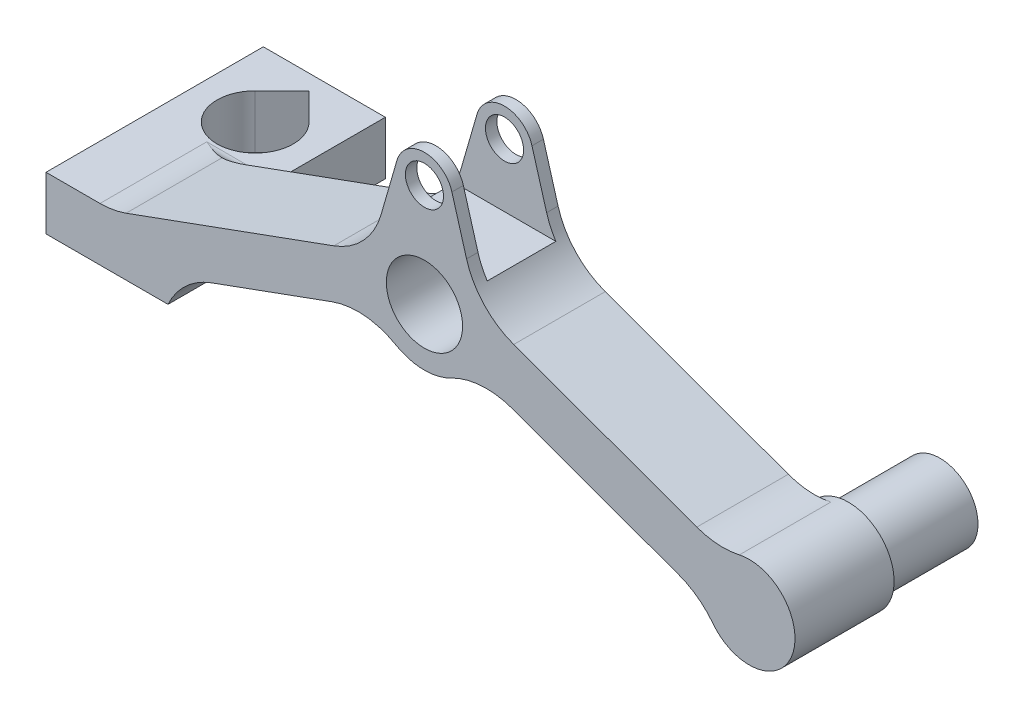
SolidWorks part; units mm, degrees
ref_plane "Alzado" through (0, 0, 0) normal (0, 0, 1) x (1, 0, 0)
ref_plane "Planta" through (0, 0, 0) normal (0, 1, 0) x (1, 0, 0)
ref_plane "Vista lateral" through (0, 0, 0) normal (1, 0, 0) x (0, 0, -1)
sketch "Croquis1" plane through (0, 0, 0) normal (0, 0, 1) x (1, 0, 0)
  line L0 (0, 0) -> (0, 13.5) construction
  line L1 (-3.6024, 14.5417) -> (-7.2048, 2.0833)
  line L2 (3.6024, 14.5417) -> (7.2048, 2.0833)
  circle A0 centre (0, 0) radius 5
  arc A1 (-7.2048, 2.0833) -> (7.2048, 2.0833) centre (0, 0) ccw
  circle A2 centre (0, 13.5) radius 2.5
  arc A3 (3.6024, 14.5417) -> (-3.6024, 14.5417) centre (0, 13.5) ccw
  dimension "D1" = 10
  dimension "D2" = 15
  dimension "D4" = 5
  dimension "D5" = 7.5
  dimension "D3" = 13.5
extrude "Saliente-Extruir1" add sketch "Croquis1" along normal mid plane 12
sketch "Croquis3" plane through (0, 0, 0) normal (1, 0, 0) x (0, 0, -1)
  line L0 (-4.5, 21.4548) -> (-4.5, 5.25)
  line L1 (-4.5, 5.25) -> (4.5, 5.25)
  line L2 (4.5, 5.25) -> (4.5, 21.4548)
  line L3 (4.5, 21.4548) -> (-4.5, 21.4548)
  line L4 (0, 0) -> (0, 21.4548) construction
  line L5 (6, 17.25) -> (-6, 17.25) construction
  point P7 (0, 21.4548)
  dimension "D1" = 9
  dimension "D2" = 12
extrude "Cortar-Extruir1" cut sketch "Croquis3" against normal through all both and the other way through all
sketch3d "Croquis3D1"
  line L0 (-5, 0, 0) -> (-41.6243, -13.3302, 0) construction
  line L1 (-41.6243, -13.3302, 0) -> (-41.6243, -13.3302, 8.998) construction
  line L2 (-41.6243, -13.3302, 8.998) -> (-5, 0, 0) construction
  line L3 (-5, 0, 0) -> (-41.6243, 0, 0) construction
  line L4 (-41.6243, 0, 0) -> (-41.6243, -13.3302, 0) construction
  line L5 (0, 0, 0) -> (-5, 0, 0) construction
  line L6 (-41.6243, -13.3302, 8.998) -> (-41.6243, -7.3302, 8.998) construction
  line L7 (0, 0, 0) -> (5, 0, 0) construction
  line L8 (5, 0, 0) -> (42.5877, -13.6808, 0) construction
  line L9 (5, 0, 0) -> (42.5877, 0, 0) construction
  line L10 (42.5877, 0, 0) -> (42.5877, -13.6808, 0) construction
  dimension "D1" = 40
  dimension "D2" = 13
  dimension "D3" = 20
  dimension "D4" = 5
  dimension "D5" = 6
  dimension "D6" = 5
  dimension "D7" = 20
  dimension "D8" = 40
ref_plane "Plano1" through (-41.6243, -13.3302, 0) normal (-0.9397, -0.342, 0) x (0, 0, 1)
sketch "Croquis4" plane through (-41.6243, -13.3302, 0) normal (-0.9397, -0.342, 0) x (0, 0, 1)
  line L1 (-6, 3) -> (6, 3)
  line L2 (-6, 3) -> (-6, -3)
  line L3 (-6, -3) -> (6, -3)
  line L4 (6, 3) -> (6, -3)
  line L5 (-6, 3) -> (6, -3) construction
  line L6 (-6, -3) -> (6, 3) construction
  point P0 (0, 0)
  dimension "D2" = 6
  dimension "D3" = 12
extrude "Saliente-Extruir2" add sketch "Croquis4" against normal blind 38
ref_plane "Plano2" through (-41.6243, -7.3302, 8.998) normal (0, 1, 0) x (1, 0, 0)
ref_plane "Plano3" through (42.5877, -13.6808, 0) normal (0.9397, -0.342, 0) x (0, 0, -1)
sketch "Croquis8" plane through (42.5877, -13.6808, 0) normal (0.9397, -0.342, 0) x (0, 0, -1)
  line L1 (-6, 3.5) -> (6, 3.5)
  line L2 (-6, 3.5) -> (-6, -3.5)
  line L3 (-6, -3.5) -> (6, -3.5)
  line L4 (6, 3.5) -> (6, -3.5)
  line L5 (-6, 3.5) -> (6, -3.5) construction
  line L6 (-6, -3.5) -> (6, 3.5) construction
  point P1 (0, 0)
  dimension "D1" = 12
  dimension "D2" = 7
extrude "Saliente-Extruir5" add sketch "Croquis8" against normal blind 39.5
sketch "Croquis9" plane through (0, 0, 0) normal (0, 0, 1) x (1, 0, 0)
  circle A0 centre (42.5877, -13.6808) radius 5
  dimension "D1" = 10
extrude "Saliente-Extruir6" add sketch "Croquis9" against normal blind 19
sketch "Croquis11" plane through (0, 0, 0) normal (0, 0, 1) x (1, 0, 0)
  line L1 (5, 0) -> (42.5877, -13.6808) construction
  line L2 (42.5877, 0) -> (42.5877, -13.6808) construction
  circle A0 centre (42.5877, -13.6808) radius 6
  dimension "D1" = 12
extrude "Saliente-Extruir7" add sketch "Croquis11" along normal mid plane 12
sketch "Croquis22" plane through (0, 0, 6) normal (0, 0, -1) x (-1, 0, 0)
  line L1 (33.6243, -16.8302) -> (49.6243, -16.8302)
  line L2 (33.6243, -16.8302) -> (33.6243, -9.8302)
  line L3 (33.6243, -9.8302) -> (49.6243, -9.8302)
  line L4 (49.6243, -16.8302) -> (49.6243, -9.8302)
  line L5 (33.6243, -16.8302) -> (49.6243, -9.8302) construction
  line L6 (33.6243, -9.8302) -> (49.6243, -16.8302) construction
  point P0 (41.6243, -13.3302)
  dimension "D1" = 7
  dimension "D2" = 16
extrude "Saliente-Extruir12" add sketch "Croquis22" along normal blind 28.5
sketch "Croquis24" plane through (0, -16.8302, 0) normal (0, -1, 0) x (1, 0, 0)
  line L0 (-41.6243, -31.5711) -> (-41.6243, -24.5) construction
  line L1 (-41.6243, -24.5) -> (-45.1599, -28.0355)
  line L2 (-41.6243, -24.5) -> (-38.0888, -28.0355)
  line L3 (-41.6243, -31.5711) -> (-41.6243, -22.5) construction
  line L4 (-33.6243, -22.5) -> (-49.6243, -22.5) construction
  line L5 (-41.6243, -22.5) -> (-43.4941, -22.5) construction
  line L6 (-33.6243, -22.5) -> (-49.6243, -22.5) construction
  line L7 (-41.6243, -20.5) -> (-38.0888, -16.9645)
  line L8 (-41.6243, -20.5) -> (-45.1599, -16.9645)
  arc A0 (-45.1599, -28.0355) -> (-38.0888, -28.0355) centre (-41.6243, -31.5711) ccw
  arc A1 (-45.1599, -16.9645) -> (-38.0888, -16.9645) centre (-41.6243, -13.4289) cw
  dimension "D1" = 10
  dimension "D2" = 90
  dimension "D3" = 2
extrude "Cortar-Extruir3" cut sketch "Croquis24" against normal blind 17
fillet "Redondeo1" radius 10 4 edges at (-6.5015, -3.739, 0) (6.2319, -4.173, 0) (6.9338, 3.0208, 0) (-7.1057, 2.4261, 0)
fillet "Redondeo2" radius 10 4 edges at (-33.6243, -13.6109, 0) (-40.7796, -9.8302, 0) (36.8111, -15.3029, 0) (39.2053, -8.7251, 0)
fillet "Redondeo3" radius 2 2 edges at (-38.0836, -9.8302, -6) (-33.6243, -13.3302, -6)
sketch "Croquis25" plane through (0, 0, -6) normal (0, 0, -1) x (-1, 0, 0)
  circle A0 centre (-42.5877, -13.6808) radius 6
extrude "Saliente-Extruir13" add sketch "Croquis25" along normal blind 1
